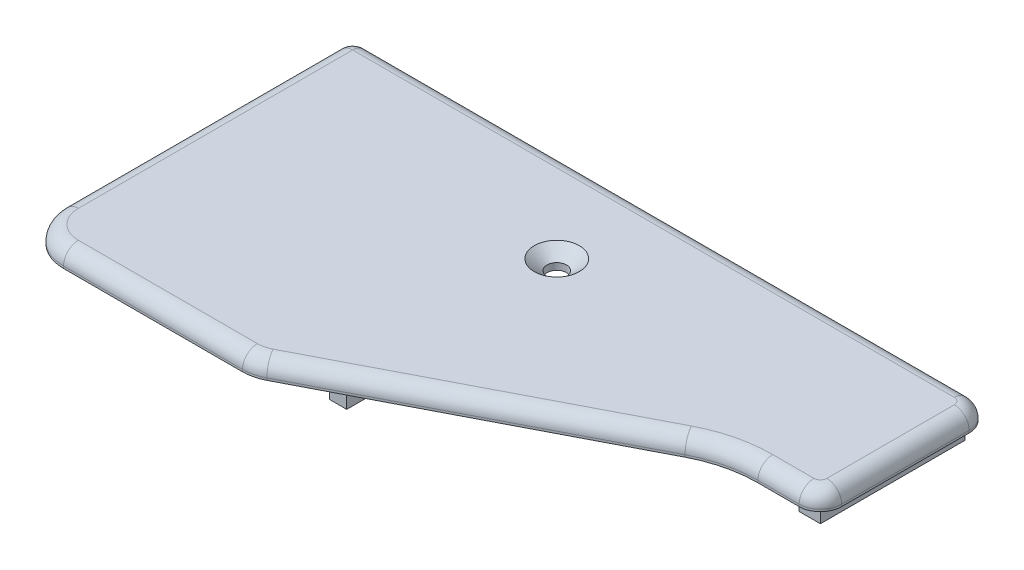
SolidWorks part; units mm, degrees
ref_plane "Front Plane" through (0, 0, 0) normal (0, 0, 1) x (1, 0, 0)
ref_plane "Top Plane" through (0, 0, 0) normal (0, 1, 0) x (1, 0, 0)
ref_plane "Right Plane" through (0, 0, 0) normal (1, 0, 0) x (0, 0, -1)
sketch "Sketch1" plane through (0, 0, 0) normal (0, 1, 0) x (1, 0, 0)
  line L5 (0, 0) -> (95.25, 0)
  line L6 (95.25, 0) -> (95.25, -25.4)
  line L7 (95.25, -25.4) -> (81.28, -25.4)
  line L8 (81.28, -25.4) -> (44.45, -44.45)
  line L9 (44.45, -44.45) -> (0, -44.45) construction
  line L10 (0, -44.45) -> (0, 0)
  line L11 (0, -44.45) -> (0, -49.53)
  line L12 (0, -49.53) -> (34.6287, -49.53)
  line L13 (34.6287, -49.53) -> (44.45, -44.45)
  circle A0 centre (44.45, -13.97) radius 1.4605
  dimension "D7" = 2.921
  dimension "D1" = 44.45
  dimension "D2" = 44.45
  dimension "D3" = 95.25
  dimension "D4" = 25.4
  dimension "D5" = 13.97
  dimension "D6" = 5.08
  dimension "D8" = 50.8
  dimension "D9" = 11.43
extrude "Boss-Extrude1" add sketch "Sketch1" along normal blind 2.54
sketch "Sketch12" plane through (0, 0, 0) normal (0, -1, 0) x (1, 0, 0)
  line L0 (95.25, 25.4) -> (95.25, 0) construction
  line L1 (90.17, 23.495) -> (93.345, 23.495)
  line L2 (90.17, 23.495) -> (90.17, 1.905)
  line L3 (90.17, 1.905) -> (93.345, 1.905)
  line L4 (93.345, 23.495) -> (93.345, 1.905)
  line L5 (81.28, 25.4) -> (95.25, 25.4) construction
  line L6 (95.25, 0) -> (0, 0) construction
  dimension "D1" = 1.905
  dimension "D2" = 1.905
  dimension "D3" = 1.905
  dimension "D4" = 3.175
extrude "Boss-Extrude7" add sketch "Sketch12" along normal blind 2.54
fillet "Fillet6" radius 19.05 1 edges at (81.28, 1.27, 25.4)
fillet "Fillet7" radius 6.35 2 edges at (0, 1.27, 49.53) (34.6287, 1.27, 49.53)
fillet "Fillet8" radius 3.175 2 edges at (95.25, 1.27, 0) (95.25, 1.27, 25.4)
fillet "Fillet9" radius 2.2225 1 edges at (0, 1.27, 0)
chamfer "Chamfer1" distance 1.905 angle 39 1 edges at (44.45, 2.54, 15.4305) first distance on face at (51.2367, 2.54, 24.7931)
fillet "Fillet10" radius 2.2225 12 edges at (0.651, 2.54, 0.651) (47.1487, 2.54, 0) (94.3201, 2.54, 0.9299) (95.25, 2.54, 12.7) (94.3201, 2.54, 24.4701) (88.995, 2.54, 25.4) (81.4114, 2.54, 25.94) (56.582, 2.54, 38.1748) (34.5849, 2.54, 49.35) (19.7168, 2.54, 49.53) (1.8599, 2.54, 47.6701) (0, 2.54, 22.7012)
sketch "Sketch13" plane through (0, 0, 0) normal (0, -1, 0) x (1, 0, 0)
  line L0 (0, 2.2225) -> (0, 43.18) construction
  line L1 (30.48, 21.844) -> (27.94, 21.844)
  line L2 (30.48, 21.844) -> (30.48, 31.369)
  line L3 (30.48, 31.369) -> (27.94, 31.369)
  line L4 (27.94, 21.844) -> (27.94, 31.369)
  line L5 (92.075, 0) -> (2.2225, 0) construction
  dimension "D1" = 2.54
  dimension "D2" = 30.48
  dimension "D3" = 9.525
  dimension "D4" = 21.844
extrude "Boss-Extrude8" add sketch "Sketch13" along normal blind 15.24
fillet "Fillet11" radius 2.54 4 edges at (29.21, 0, 21.844) (30.48, 0, 26.6065) (29.21, 0, 31.369) (27.94, 0, 26.6065)
sketch "Sketch14" plane through (27.94, 0, 0) normal (-1, 0, 0) x (0, 0, 1)
  line L0 (26.6065, -15.24) -> (26.6065, -2.54) construction
  line L1 (31.369, -15.24) -> (21.844, -15.24) construction
  line L2 (31.369, -2.54) -> (21.844, -2.54) construction
  line L3 (21.844, -8.89) -> (31.369, -8.89) construction
  line L4 (21.844, -15.24) -> (21.844, -2.54) construction
  line L5 (31.369, -15.24) -> (31.369, -2.54) construction
  circle A0 centre (26.6065, -8.89) radius 3.175
  dimension "D1" = 6.35
extrude "Cut-Extrude1" cut sketch "Sketch14" against normal through all
